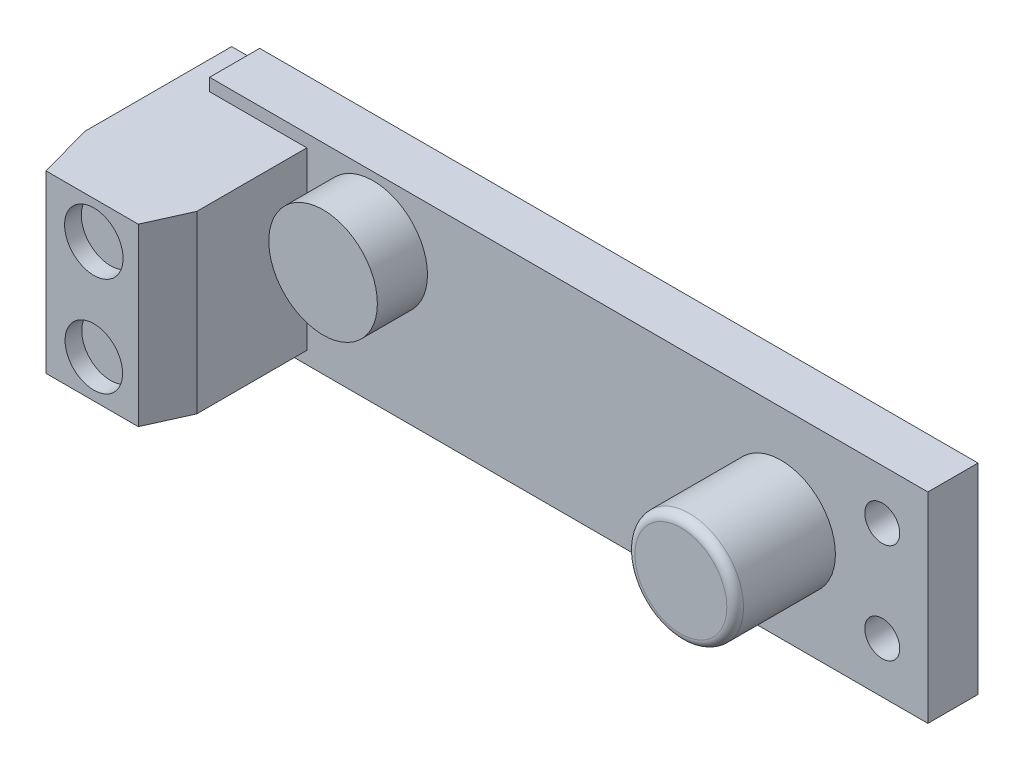
SolidWorks part; units mm, degrees
ref_plane "Plan de face" through (0, 0, 0) normal (0, 0, 1) x (1, 0, 0)
ref_plane "Plan de dessus" through (0, 0, 0) normal (0, 1, 0) x (1, 0, 0)
ref_plane "Plan de droite" through (0, 0, 0) normal (1, 0, 0) x (0, 0, -1)
sketch "Esquisse1" plane through (0, 0, 0) normal (0, 0, 1) x (1, 0, 0)
  line L1 (-21.5, -6) -> (21.5, -6)
  line L2 (-21.5, -6) -> (-21.5, 6)
  line L3 (-21.5, 6) -> (21.5, 6)
  line L4 (21.5, -6) -> (21.5, 6)
  line L5 (-21.5, -6) -> (21.5, 6) construction
  line L6 (-21.5, 6) -> (21.5, -6) construction
  line L7 (-23.1807, 5.25) -> (-15.6807, 5.25)
  line L8 (-23.1807, 5.25) -> (-23.1807, -5.25)
  line L9 (-23.1807, -5.25) -> (-15.6807, -5.25)
  line L10 (-15.6807, 5.25) -> (-15.6807, -5.25)
  line L11 (-23.1807, 5.25) -> (-15.6807, -5.25) construction
  line L12 (-23.1807, -5.25) -> (-15.6807, 5.25) construction
  circle A0 centre (-11.7061, 2.2805) radius 3.25
  circle A1 centre (12.7136, 0) radius 3.25
  circle A2 centre (18.7679, 3.0128) radius 1.0477
  circle A3 centre (18.7679, -2.9634) radius 1.0477
  circle A4 centre (-19.4307, 3.0128) radius 1.7512
  circle A5 centre (-19.4307, -2.9634) radius 1.7225
  point P0 (0, 0)
  point P6 (-19.4307, 0)
extrude "Boss.-Extru.1" add sketch "Esquisse1" against normal blind 3 contours L7 L10 L9 L2 L1 L4 L3 A3 A2 A1 A0 region at (2.5497, -0.1987, 0)
extrude "Boss.-Extru.2" add sketch "Esquisse1<3>" along normal blind 3 and the other way blind 3 contours A0 region at (-11.7061, 2.2805, 0)
sketch "Esquisse1<3>" plane through (0, 0, 0) normal (0, 0, 1) x (1, 0, 0) same geometry as "Esquisse1"
extrude "Boss.-Extru.3" add sketch "Esquisse1<4>" along normal blind 6 and the other way blind 3 contours A1 region at (12.7136, 0, 0)
sketch "Esquisse1<4>" plane through (0, 0, 0) normal (0, 0, 1) x (1, 0, 0) same geometry as "Esquisse1"
extrude "Boss.-Extru.4" add sketch "Esquisse1<5>" along normal blind 9 and the other way blind 3 contours L10 L7 L2 L9 A5 A4 | L8 L9 L2 L7 region at (-22.3403, 0, 0) region at (-18.2124, -0.0333, 0)
sketch "Esquisse1<5>" plane through (0, 0, 0) normal (0, 0, 1) x (1, 0, 0) same geometry as "Esquisse1"
extrude "Boss.-Extru.5" add sketch "Esquisse1<6>" along normal blind 8 and the other way blind 3 contours A4 | A5 region at (-19.4307, 3.0128, 0) region at (-19.4307, -2.9634, 0)
sketch "Esquisse1<6>" plane through (0, 0, 0) normal (0, 0, 1) x (1, 0, 0) same geometry as "Esquisse1"
sketch "Esquisse2" plane through (0, 0, 0) normal (0, 1, 0) x (1, 0, 0)
  line L0 (-23.1807, -5.7907) -> (-22.2937, -9)
  line L1 (-23.1807, 3) -> (-23.1807, -9) construction
  line L2 (-23.1807, -9) -> (-15.6807, -9) construction
  line L3 (-22.2937, -9) -> (-23.1807, -9)
  line L4 (-23.1807, -9) -> (-23.1807, -5.7907)
  line L5 (-15.6807, -6.5863) -> (-16.7691, -9)
  line L6 (-15.6807, 0) -> (-15.6807, -9) construction
  line L7 (-16.7691, -9) -> (-15.6807, -9)
  line L8 (-15.6807, -9) -> (-15.6807, -6.5863)
extrude "Enlèv. mat.-Extru.1" cut sketch "Esquisse2" against normal blind 8 and the other way blind 8
fillet "Congé1" radius 0.5 1 edges at (15.9636, 0, 6)
